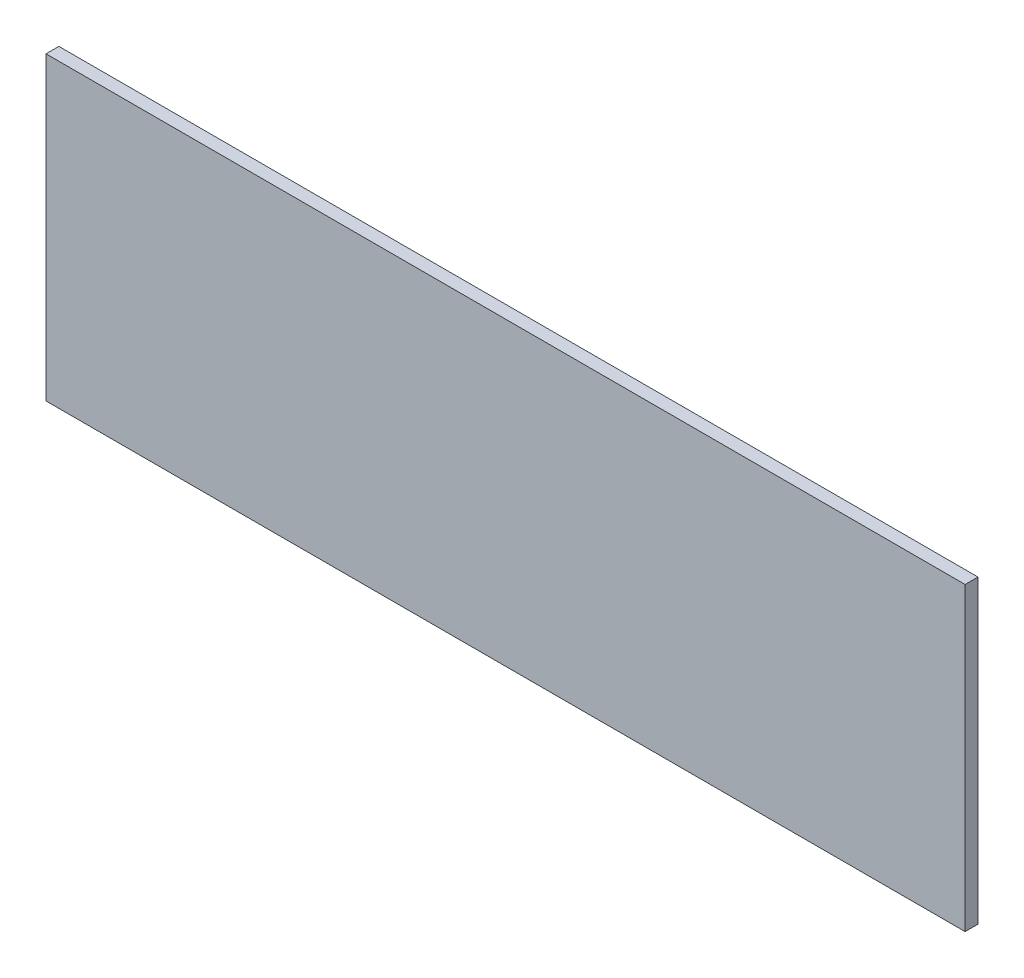
SolidWorks part; units mm, degrees
ref_plane "Front Plane" through (0, 0, 0) normal (0, 0, 1) x (1, 0, 0)
ref_plane "Top Plane" through (0, 0, 0) normal (0, 1, 0) x (1, 0, 0)
ref_plane "Right Plane" through (0, 0, 0) normal (1, 0, 0) x (0, 0, -1)
sketch "Sketch1" plane through (0, 0, 0) normal (0, 0, 1) x (1, 0, 0)
  line L1 (6, 250) -> (434, 250)
  line L2 (6, 250) -> (6, 110)
  line L3 (6, 110) -> (434, 110)
  line L4 (434, 250) -> (434, 110)
extrude "Boss-Extrude1" add sketch "Sketch1" against normal blind 6 contours L2 L3 L4 L1
